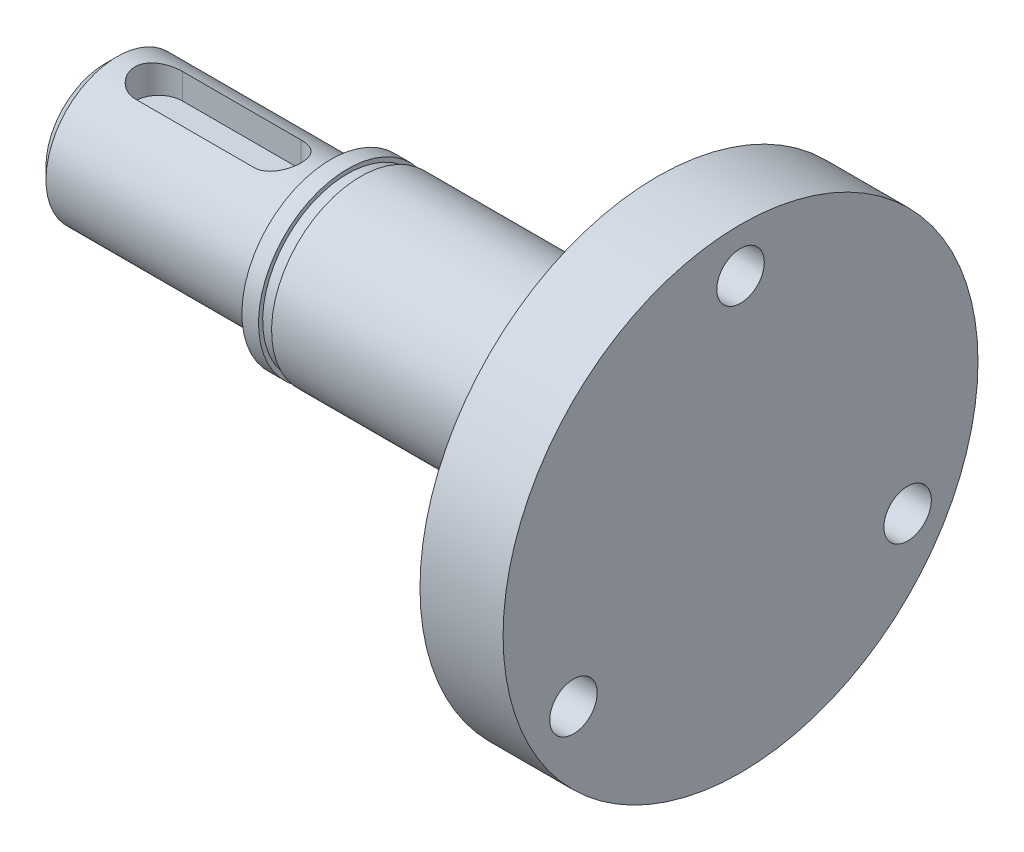
SolidWorks part; units mm, degrees
material "AISI 4340 Steel, normalized"
ref_plane "Front Plane" through (0, 0, 0) normal (0, 0, 1) x (1, 0, 0)
ref_plane "Top Plane" through (0, 0, 0) normal (0, 1, 0) x (1, 0, 0)
ref_plane "Right Plane" through (0, 0, 0) normal (1, 0, 0) x (0, 0, -1)
sketch "Sketch1" plane through (0, 0, 0) normal (0, 0, 1) x (1, 0, 0)
  line L0 (0, 0) -> (0, 5)
  line L3 (19, 6) -> (1, 6)
  line L5 (1, 6) -> (0, 5)
  line L6 (19, 6) -> (19, 7.5)
  line L7 (20.4, 7.15) -> (20.4, 7.5)
  line L9 (21.5, 7.15) -> (21.5, 7.5)
  line L10 (0, 0) -> (53.5, 0)
  line L11 (46, 7.5) -> (46, 10)
  line L12 (19, 7.5) -> (20.4, 7.5)
  line L14 (53.5, 0) -> (53.5, 20)
  line L17 (46, 10) -> (46.5, 10)
  line L19 (46.5, 20) -> (53.5, 20)
  line L24 (20.4, 7.15) -> (21.5, 7.15)
  line L25 (21.5, 7.5) -> (46, 7.5)
  line L27 (46.5, 10) -> (46.5, 20)
revolve "Revolve3" add sketch "Sketch1" angle 360 about L10
hole_wizard "Ø4.0 (4) Diameter Hole1" positions "Sketch4" profile "Sketch3" hole size "Ø4.0" standard "DIN"
sketch "Sketch4" plane through (53.5, 0, 0) normal (1, 0, 0) x (0, 0, -1)
  point P0 (0, 16.25)
  dimension "D1" = 16.25
sketch "Sketch3" plane through (53.5, 16.25, 0) normal (0, 1, 0) x (0, 0, -1)
  line L0 (0, 0) -> (0, 13.2017)
  line L1 (0, 13.2017) -> (2, 12)
  line L2 (2, 12) -> (2, 0)
  line L5 (2, 0) -> (0, 0)
  line L10 (0, 13.2017) -> (-2, 12) construction
  line L11 (0, -6.35) -> (0, 107.95) construction
  dimension "Hole Dia." = 4
  dimension "Hole Depth" = 12
  dimension "Drill Angle" = 118
ref_axis "Axis1" through (53.5, 0, 0) along (-1, 0, 0)
pattern_circular "CirPattern1" count 3 over 360 about axis through (53.5, 0, 0) along (-1, 0, 0) of "Ø4.0 (4) Diameter Hole1"
sketch "Sketch6" plane through (0, 0, 0) normal (0, 1, 0) x (1, 0, 0)
  line L0 (0, 0) -> (19, 0) construction
  line L1 (4.5, -2) -> (14.5, -2)
  line L2 (4.5, 2) -> (14.5, 2)
  arc A0 (4.5, 2) -> (4.5, -2) centre (4.5, 0) ccw
  arc A1 (14.5, -2) -> (14.5, 2) centre (14.5, 0) ccw
  dimension "D2" = 2
  dimension "D1" = 10
extrude "Cut-Extrude1" cut sketch "Sketch6" against normal blind 2.5 from offset 6
scale "Echelle1" scale about centroid uniform scaling yes scale factor 2
scale "Echelle2" scale about centroid uniform scaling yes scale factor 0.25
